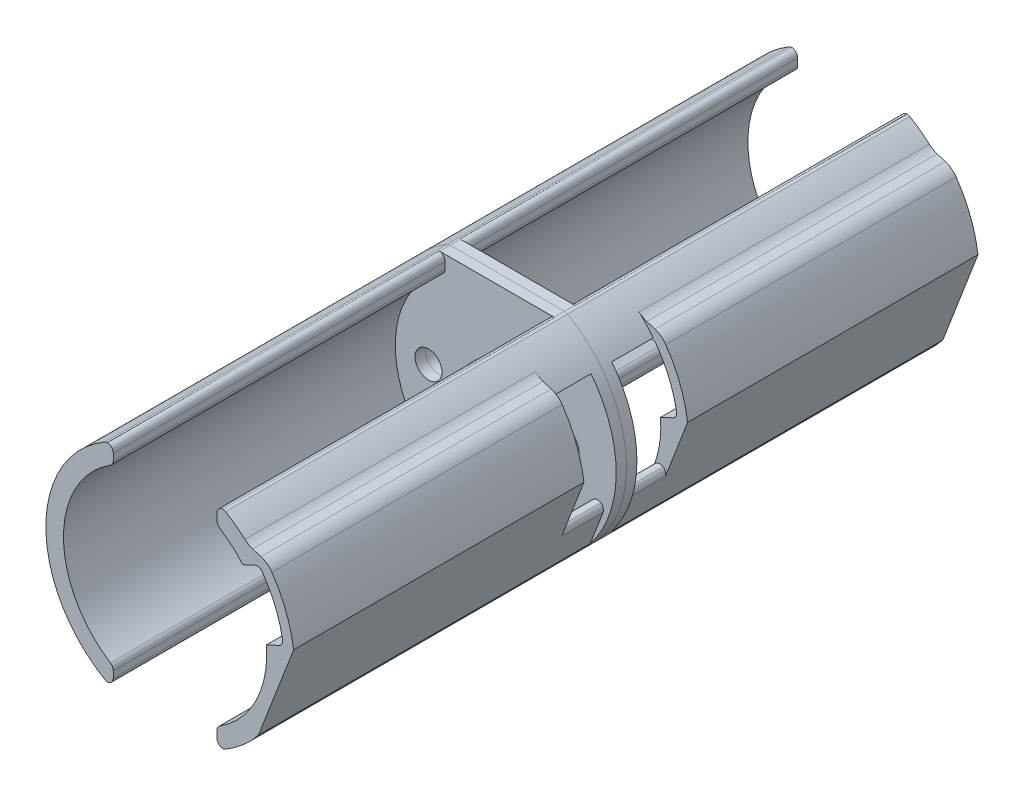
SolidWorks part; units mm, degrees
ref_plane "Front Plane" through (0, 0, 0) normal (0, 0, 1) x (1, 0, 0)
ref_plane "Top Plane" through (0, 0, 0) normal (0, 1, 0) x (1, 0, 0)
ref_plane "Right Plane" through (0, 0, 0) normal (1, 0, 0) x (0, 0, -1)
sketch "Sketch1" plane through (0, 0, 0) normal (0, 0, 1) x (1, 0, 0)
  circle A0 centre (0, 0) radius 12.446
  circle A1 centre (0, 0) radius 14.605
  dimension "D1" = 24.892
  dimension "D2" = 29.21
extrude "Boss-Extrude1" add sketch "Sketch1" along normal blind 40.64
sketch "Sketch2" plane through (0, 0, 0) normal (0, 0, -1) x (-1, 0, 0)
  circle A0 centre (0, 0) radius 14.605
  circle A1 centre (0, 0) radius 3.556
  circle A2 centre (-8.382, 0) radius 1.651
  circle A3 centre (8.382, 0) radius 1.651
  dimension "D1" = 7.112
  dimension "D4" = 3.302
  dimension "D2" = 16.764
  dimension "D3" = 8.382
extrude "Boss-Extrude2" add sketch "Sketch2" along normal blind 1.27
sketch "Sketch3" plane through (0, 0, -1.27) normal (0, 0, -1) x (-1, 0, 0)
  line L1 (-16.4466, 19.1182) -> (17.6099, 19.1182)
  line L2 (-16.4466, 19.1182) -> (-16.4466, 12.7)
  line L3 (-16.4466, 12.7) -> (17.6099, 12.7)
  line L4 (17.6099, 19.1182) -> (17.6099, 12.7)
  line L5 (-16.4466, -18.2758) -> (18.5325, -18.2758)
  line L6 (-16.4466, -18.2758) -> (-16.4466, -12.7)
  line L7 (-16.4466, -12.7) -> (18.5325, -12.7)
  line L8 (18.5325, -18.2758) -> (18.5325, -12.7)
  dimension "D1" = 25.4
  dimension "D2" = 12.7
extrude "Cut-Extrude1" cut sketch "Sketch3" against normal through all
sketch "Sketch4" plane through (0, 12.7, 0) normal (0, 1, 0) x (1, 0, 0)
  line L0 (7.2122, 1.27) -> (-7.2122, 1.27) construction
  line L1 (-6.35, -40.64) -> (6.35, -40.64)
  line L2 (-6.35, -40.64) -> (-6.35, 0)
  line L3 (-6.35, 0) -> (6.35, 0)
  line L4 (6.35, -40.64) -> (6.35, 0)
  line L5 (7.2122, -40.64) -> (-7.2122, -40.64) construction
  dimension "D1" = 1.27
  dimension "D2" = 12.7
  dimension "D3" = 6.35
extrude "Cut-Extrude2" cut sketch "Sketch4" against normal through all
sketch "Sketch5" plane through (0, 0, 40.64) normal (0, 0, 1) x (1, 0, 0)
  line L1 (8.707, 7.6569) -> (15.1561, 10.6642)
  line L2 (8.707, 7.6569) -> (11.9273, 0.7509)
  line L3 (11.9273, 0.7509) -> (18.3764, 3.7582)
  line L4 (15.1561, 10.6642) -> (18.3764, 3.7582)
  dimension "D1" = 7.62
extrude "Cut-Extrude3" cut sketch "Sketch5" against normal up to surface (40.64 mm away) up to face at (0, 0, 0)
sketch "Sketch6" plane through (0, 0, -1.27) normal (0, 0, -1) x (-1, 0, 0)
  line L0 (0, 0) -> (-14.6385, 6.1425) construction
  line L4 (-12.5272, 9.7511) -> (-10.1697, 10.4826)
  line L5 (-15.7344, 2.1078) -> (-14.6047, -0.0869)
  arc A1 (-7.2122, 12.7) -> (-11.525, 8.971) centre (0, 0) ccw construction
  arc A2 (-12.5272, 9.7511) -> (-15.7344, 2.1078) centre (0, 0) ccw
  arc A3 (-12.5272, 9.7511) -> (-15.7344, 2.1078) centre (0, 0) ccw
  arc A4 (-14.4757, 1.9392) -> (-7.2122, -12.7) centre (0, 0) ccw construction
  arc A5 (-11.525, 8.971) -> (-14.4757, 1.9392) centre (0, 0) ccw construction
  arc A6 (-11.525, 8.971) -> (-14.4757, 1.9392) centre (0, 0) ccw
  arc A7 (-10.1697, 10.4826) -> (-11.525, 8.971) centre (0, 0) ccw
  arc A8 (-14.4757, 1.9392) -> (-14.6047, -0.0869) centre (0, 0) ccw
  dimension "D2" = 80
  dimension "D3" = 40
  dimension "D1" = 1.27
extrude "Boss-Extrude3" add sketch "Sketch6" against normal up to surface (41.91 mm away) up to face at (8.2483, 10.6901, 40.64)
sketch "Sketch7" plane through (0, 0, -1.27) normal (0, 0, -1) x (-1, 0, 0)
  circle A0 centre (0, 0) radius 14.605
  circle A1 centre (0, 0) radius 15.875
extrude "Cut-Extrude4" cut sketch "Sketch7" against normal blind 6.35
sketch "Sketch8" plane through (0, 0, 0) normal (0, 0, 1) x (1, 0, 0)
  line L0 (12.4078, 0.9749) -> (14.4757, 1.9392) construction
  line L1 (12.4078, 0.9749) -> (14.4757, 1.9392)
  line L2 (11.9313, -3.5423) -> (13.7807, -4.8373)
  line L3 (0, 0) -> (14.5494, -1.2729) construction
  arc A0 (6.35, -10.7042) -> (12.4078, 0.9749) centre (0, 0) ccw construction
  arc A1 (11.9313, -3.5423) -> (12.4078, 0.9749) centre (0, 0) ccw
  arc A2 (7.2122, -12.7) -> (14.6047, -0.0869) centre (0, 0) ccw construction
  arc A3 (13.7807, -4.8373) -> (14.4686, 1.9911) centre (0, 0) ccw
  arc M1 (6.35, -10.7042) -> (12.4078, 0.9749) centre (0, 0) ccw
  line M2 (12.4078, 0.9749) -> (14.4757, 1.9392)
  dimension "D1" = 60
  dimension "D2" = 30
extrude "Cut-Extrude5" cut sketch "Sketch8" along normal blind 5.08 contours A1 L3 A3 M2 | L3 L2 A3 M1
sketch "Sketch11" plane through (0, 0, 40.64) normal (0, 0, 1) x (1, 0, 0)
  line L0 (15.7344, 2.1078) -> (11.4289, -9.0932)
  line L1 (11.4289, -9.0932) -> (14.3925, -10.2323)
  line L2 (14.3925, -10.2323) -> (18.698, 0.9687)
  line L3 (18.698, 0.9687) -> (15.7344, 2.1078)
  line L4 (7.2122, -12.7) -> (20.3584, -12.7) construction
  arc A0 (7.2122, -12.7) -> (14.6047, -0.0869) centre (0, 0) ccw construction
  dimension "D1" = 12
  dimension "D2" = 3.175
extrude "Cut-Extrude6" cut sketch "Sketch11" against normal up to surface (40.64 mm away) up to face at (3.5999, 0.7096, 0)
sketch "Sketch12" plane through (0, 0, 40.64) normal (0, 0, 1) x (1, 0, 0)
  line L1 (14.577, -0.9032) -> (15.7344, 2.1078)
  line L2 (15.7344, 2.1078) -> (15.1557, 2.3303)
  line L3 (15.1557, 2.3303) -> (13.9983, -0.6807)
  line L4 (13.9983, -0.6807) -> (14.577, -0.9032)
extrude "Boss-Extrude5" add sketch "Sketch12" against normal up to surface (35.56 mm away)
fillet "Fillet1" radius 0.762 15 edges at (-3.556, 0, 0) (-7.2122, -12.7, 19.685) (-6.35, -12.7, 20.32) (-6.35, 10.7042, 20.32) (-6.35, -10.7042, 20.32) (6.35, -12.7, 20.32) (6.35, -10.7042, 20.32) (6.35, 10.7042, 20.32) (6.35, 12.7, 20.32) (-7.2122, 12.7, 19.685) (-6.35, 12.7, 20.32) (13.2166, -4.4423, 2.54) (11.9313, -3.5423, 2.54) (11.525, 8.971, 22.86) (14.4757, 1.9392, 22.86)
fillet "Fillet2" radius 2.54 2 edges at (12.5272, 9.7511, 22.86) (10.1697, 10.4826, 22.86)
mirror "Mirror1" about plane through (0, 0, -1.27) normal (0, 0, -1) of bodies 111
equation "\"D3@Sketch4\"=\"D2@Sketch4\"/2"
